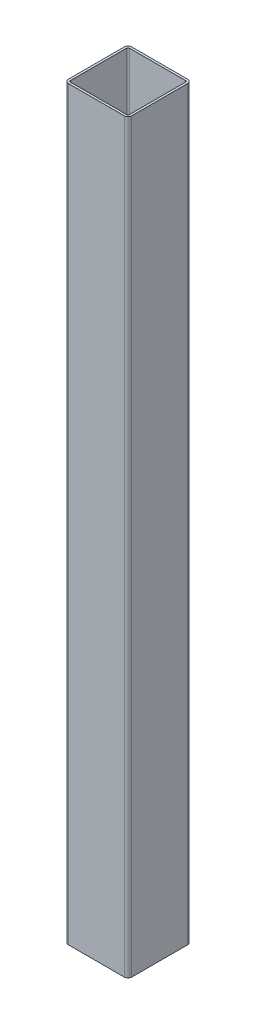
SolidWorks part; units mm, degrees
ref_plane "Спереди" through (0, 0, 0) normal (0, 0, 1) x (1, 0, 0)
ref_plane "Сверху" through (0, 0, 0) normal (0, 1, 0) x (1, 0, 0)
ref_plane "Справа" through (0, 0, 0) normal (1, 0, 0) x (0, 0, -1)
sketch "Эскиз1" plane through (0, 0, 0) normal (0, 1, 0) x (1, 0, 0)
  line L1 (-37.5, 42.5) -> (37.5, 42.5)
  line L2 (-42.5, 37.5) -> (-42.5, -37.5)
  line L3 (-37.5, -42.5) -> (37.5, -42.5)
  line L4 (42.5, 37.5) -> (42.5, -37.5)
  line L5 (-42.5, 42.5) -> (42.5, -42.5) construction
  line L6 (-42.5, -42.5) -> (42.5, 42.5) construction
  arc A0 (37.5, -42.5) -> (42.5, -37.5) centre (37.5, -37.5) ccw
  arc A1 (37.5, 42.5) -> (42.5, 37.5) centre (37.5, 37.5) cw
  arc A2 (-37.5, 42.5) -> (-42.5, 37.5) centre (-37.5, 37.5) ccw
  arc A3 (-42.5, -37.5) -> (-37.5, -42.5) centre (-37.5, -37.5) ccw
  point P0 (0, 0)
  dimension "D3" = 5
  dimension "D1" = 85
  dimension "D2" = 85
extrude "Вытянуть-Тонкостенный1" add sketch "Эскиз1" along normal blind 1000 thin thin type one direction reverse wall 3
